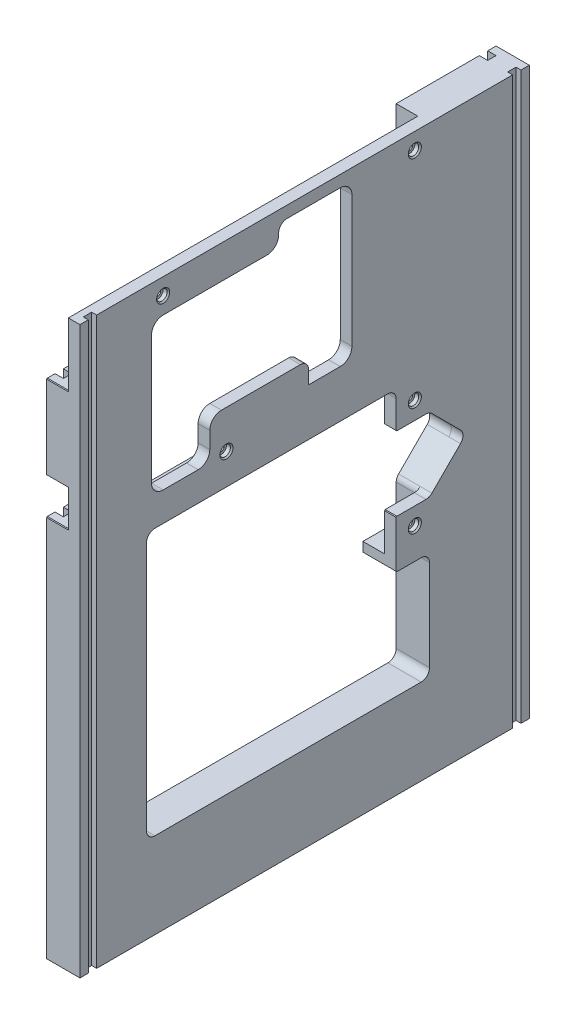
SolidWorks part; units mm, degrees
ref_plane "Front Plane" through (0, 0, 0) normal (0, 0, 1) x (1, 0, 0)
ref_plane "Top Plane" through (0, 0, 0) normal (0, 1, 0) x (1, 0, 0)
ref_plane "Right Plane" through (0, 0, 0) normal (1, 0, 0) x (0, 0, -1)
sketch "Sketch2" plane through (0, 0, 0) normal (1, 0, 0) x (0, 0, -1)
  line L1 (-215.489, 137.2751) -> (127.411, 137.2751)
  line L2 (-215.489, 137.2751) -> (-215.489, -294.5249)
  line L3 (-215.489, -294.5249) -> (127.411, -294.5249)
  line L4 (127.411, 137.2751) -> (127.411, -294.5249)
  dimension "D1" = 342.9
  dimension "D2" = 431.8
extrude "Base" add sketch "Sketch2" along normal blind 25.4
sketch "Sketch3" plane through (0, 0, 0) normal (1, 0, 0) x (0, 0, -1)
  line L0 (-44.039, -294.5249) -> (-44.039, 137.2751) construction
  line L1 (-215.489, -294.5249) -> (127.411, -294.5249) construction
  line L2 (-164.689, -25.9199) -> (-164.689, -229.1199)
  line L3 (-164.689, -229.1199) -> (51.211, -229.1199)
  line L4 (51.211, -146.9509) -> (51.211, -229.1199)
  line L5 (127.411, 137.2751) -> (-215.489, 137.2751) construction
  line L7 (-215.489, 137.2751) -> (-215.489, -294.5249) construction
  line L9 (51.211, -146.9509) -> (25.811, -146.9509)
  line L13 (-164.689, -25.9199) -> (25.811, -25.9199)
  line L14 (25.811, -146.9509) -> (25.811, -25.9199)
  dimension "D1" = 25.4
  dimension "D2" = 163.195
  dimension "D3" = 50.8
  dimension "D4" = 121.031
  dimension "D5" = 190.5
  dimension "D6" = 203.2
extrude "Cut-Extrude3" cut sketch "Sketch3" along normal up to next
sketch "Sketch4" plane through (0, 0, 0) normal (1, 0, 0) x (0, 0, -1)
  line L0 (-215.489, 137.2751) -> (-215.489, -294.5249) construction
  line L1 (19.461, -18.2999) -> (-158.339, -18.2999)
  line L2 (51.211, -15.1249) -> (51.211, 137.2751)
  line L3 (51.211, 137.2751) -> (-202.789, 137.2751)
  line L4 (-164.689, -12.5837) -> (-164.689, -2.4249)
  line L5 (51.211, -146.9509) -> (25.811, -146.9509) construction
  line L6 (25.811, -25.9199) -> (-164.689, -25.9199) construction
  line L7 (-164.689, 24.8801) -> (-215.489, 24.8801)
  line L8 (51.211, -15.1249) -> (51.211, -53.8599)
  line L9 (44.861, -139.3309) -> (25.811, -139.3309)
  line L10 (25.811, -25.9199) -> (25.811, -139.3309)
  line L11 (25.811, -25.9199) -> (-164.689, -25.9199) construction
  line L12 (25.811, -25.9199) -> (19.461, -25.9199)
  line L13 (19.461, -18.2999) -> (19.461, -25.9199)
  line L14 (51.211, -136.1559) -> (51.211, -146.9509)
  line L15 (51.211, -146.9509) -> (44.861, -146.9509)
  line L16 (44.861, -139.3309) -> (44.861, -146.9509)
  line L17 (-44.039, 137.2751) -> (-44.039, -294.5249) construction
  line L18 (-164.689, -12.5837) -> (-164.689, -25.9199)
  line L19 (-164.689, -25.9199) -> (-158.339, -25.9199)
  line L20 (-158.339, -18.2999) -> (-158.339, -25.9199)
  line L22 (-215.489, -294.5249) -> (127.411, -294.5249) construction
  line L23 (51.211, -110.2479) -> (79.405, -82.0539)
  line L24 (-164.689, -2.4249) -> (-215.489, -2.4249)
  line L25 (-215.489, 24.8801) -> (-215.489, -2.4249)
  line L26 (-164.689, 24.8801) -> (-164.689, 89.0151)
  line L27 (-202.789, 137.2751) -> (-215.489, 137.2751)
  line L28 (79.405, -82.0539) -> (51.211, -53.8599)
  line L29 (-164.689, 89.0151) -> (-215.489, 89.0151)
  line L30 (-215.489, 137.2751) -> (-215.489, 90.2851)
  line L31 (-215.489, 90.2851) -> (-215.489, 89.0151)
  line L32 (51.211, -110.2479) -> (51.211, -136.1559)
  dimension "D2" = 7.62
  dimension "D3" = 15.875
  dimension "D4" = 276.606
  dimension "D5" = 25.4
  dimension "D6" = 6.35
  dimension "D7" = 6.35
  dimension "D8" = 7.62
  dimension "D9" = 6.35
  dimension "D10" = 48.26
  dimension "D11" = 43.18
  dimension "D12" = 215.9
  dimension "D13" = 266.7
  dimension "D15" = 45
  dimension "D16" = 29.083
  dimension "D17" = 56.388
extrude "NC pocket" cut sketch "Sketch4" along normal blind 16.51
fillet "Fillet9" radius 6.35 2 edges at (8.255, -110.2479, -51.211) (8.255, -53.8599, -51.211)
fillet "Fillet6" radius 6.35 1 edges at (8.255, -82.0539, -79.405)
hole_wizard "CBORE for M4 SHCS1" positions "Sketch8" profile "Sketch10" counterbore size "M4" standard "ANSI Metric" end condition up to next
sketch "Sketch8" plane through (25.4, 0, 0) normal (1, 0, 0) x (0, 0, -1)
  line L1 (127.411, 137.2751) -> (-215.489, 137.2751) construction
  line L4 (-164.689, -2.4249) -> (-164.689, -229.1199) construction
  line L5 (51.211, -229.1199) -> (51.211, -112.8782) construction
  line L6 (-158.339, -18.2999) -> (19.461, -18.2999) construction
  point P0 (-151.989, 124.5751)
  point P5 (40.035, 124.5751)
  point P7 (40.035, -123.4559)
  point P9 (40.035, -40.5249)
  point P11 (-103.729, -2.4249)
  dimension "D2" = 12.7
  dimension "D3" = 12.7
  dimension "D4" = 11.176
  dimension "D5" = 60.96
  dimension "D6" = 15.875
  dimension "D7" = 11.176
  dimension "D8" = 165.1
  dimension "D9" = 11.176
  dimension "D10" = 82.931
  dimension "D11" = 12.7
sketch "Sketch10" plane through (25.4, 124.5751, 151.989) normal (0, 1, 0) x (0, 0, -1)
  line L0 (0, 0) -> (0, 8.89)
  line L1 (0, 8.89) -> (2.15, 8.89)
  line L3 (2.15, 8.89) -> (2.15, 4)
  line L4 (4, 4) -> (2.15, 4)
  line L5 (4, 4) -> (4, 1)
  line L6 (4, 1) -> (5, 0)
  line L7 (5, 0) -> (0, 0)
  line L8 (-4, 1) -> (-5, 0) construction
  line L11 (0, -6.35) -> (0, 107.95) construction
  dimension "Thru Hole Dia." = 4.3
  dimension "Thru Hole Depth" = 8.89
  dimension "C'Bore Dia." = 8
  dimension "C'Bore Depth" = 4
  dimension "Near C'Sink Dia." = 10
  dimension "Near C'Sink Angle" = 90
sketch "Sketch18" plane through (16.51, 0, 0) normal (-1, 0, 0) x (0, 0, 1)
  circle A0 centre (-40.035, 124.5751) radius 7.1755
  circle A1 centre (151.989, 124.5751) radius 7.1755
  circle A2 centre (103.729, -2.4249) radius 7.1755
  circle A3 centre (-40.035, -40.5249) radius 7.1755
  circle A4 centre (-40.035, -123.4559) radius 7.1755
  dimension "D1" = 14.351
  dimension "D2" = 14.351
  dimension "D3" = 14.351
  dimension "D4" = 14.351
  dimension "D5" = 14.351
extrude "Cut-Extrude4" cut sketch "Sketch18" against normal blind 1.016
hole_wizard "3/8-16 Tapped Hole1" positions "3DSketch1" profile "Sketch14" tap size "3/8-16" standard "ANSI Inch"
sketch3d "3DSketch1"
  line L0 (0, -294.5249, 215.489) -> (0, -294.5249, -127.411) construction
  line L1 (25.4, -294.5249, 215.489) -> (0, -294.5249, 215.489) construction
  point P0 (12.7, -294.5249, -70.261)
  point P2 (12.7, -294.5249, 44.039)
  point P4 (12.7, -294.5249, 158.339)
  dimension "D1" = 12.7
  dimension "D2" = 12.7
  dimension "D3" = 12.7
  dimension "D4" = 114.3
  dimension "D6" = 114.3
  dimension "D5" = 171.45
sketch "Sketch14" plane through (12.7, -294.5249, -70.261) normal (1, 0, 0) x (0, 0, -1)
  line L0 (0, 0) -> (0, 30.3247)
  line L1 (0, 30.3247) -> (3.9687, 27.94)
  line L2 (3.9687, 27.94) -> (3.9687, 0)
  line L5 (3.9687, 0) -> (0, 0)
  line L10 (0, 30.3247) -> (-3.9688, 27.94) construction
  line L11 (0, -6.35) -> (0, 107.95) construction
  dimension "Tap Drill Dia." = 7.9375
  dimension "Tap Drill Depth" = 27.94
  dimension "Drill Angle" = 118
cosmetic thread "Hole Thread1" parameters "D1"=25.4, "D2"=9.525
cosmetic thread "Hole Thread2" parameters "D1"=25.4, "D2"=9.525
cosmetic thread "Hole Thread3" parameters "D1"=25.4, "D2"=9.525
hole_wizard "3/8-16 Tapped Hole2" positions "Sketch15" profile "Sketch17" tap size "3/8-16" standard "ANSI Inch"
sketch "Sketch15" plane through (0, 0, 0) normal (-1, 0, 0) x (0, 0, 1)
  line L0 (215.489, -2.4249) -> (215.489, -294.5249) construction
  line L1 (-127.411, -294.5249) -> (-127.411, 137.2751) construction
  line L2 (215.489, -294.5249) -> (-127.411, -294.5249) construction
  point P0 (190.089, -220.8649)
  point P2 (190.089, -162.4449)
  point P4 (-102.011, -220.8649)
  point P6 (-102.011, -162.4449)
  dimension "D1" = 25.4
  dimension "D2" = 25.4
  dimension "D3" = 25.4
  dimension "D4" = 25.4
  dimension "D5" = 73.66
  dimension "D6" = 58.42
  dimension "D7" = 58.42
  dimension "D8" = 73.66
cosmetic thread "Hole Thread4" parameters "D1"=17.78, "D2"=9.525
cosmetic thread "Hole Thread5" parameters "D1"=17.78, "D2"=9.525
cosmetic thread "Hole Thread6" parameters "D1"=17.78, "D2"=9.525
cosmetic thread "Hole Thread7" parameters "D1"=17.78, "D2"=9.525
sketch "Sketch17" plane through (0, -220.8649, 190.089) normal (0, 1, 0) x (0, 0, 1)
  line L0 (0, 0) -> (0, 22.7047)
  line L1 (0, 22.7047) -> (3.9687, 20.32)
  line L2 (3.9687, 20.32) -> (3.9687, 0)
  line L5 (3.9687, 0) -> (0, 0)
  line L10 (0, 22.7047) -> (-3.9688, 20.32) construction
  line L11 (0, -6.35) -> (0, 107.95) construction
  dimension "Tap Drill Dia." = 7.9375
  dimension "Tap Drill Depth" = 20.32
  dimension "Drill Angle" = 118
sketch "Sketch20" plane through (16.51, 0, 0) normal (-1, 0, 0) x (0, 0, 1)
  line L0 (-51.211, -53.8599) -> (-25.811, -53.8599)
  line L2 (-51.211, -53.8599) -> (-79.405, -82.0539)
  line L3 (-79.405, -82.0539) -> (-51.211, -110.2479)
  line L4 (-25.811, -25.9199) -> (-25.811, -139.3309) construction
  line L6 (-25.811, -53.8599) -> (-25.811, -110.2479)
  line L7 (-25.811, -110.2479) -> (-51.211, -110.2479)
  line L8 (-51.211, -45.3946) -> (-51.211, -54.9122) construction
  line L9 (-51.211, -51.2297) -> (-51.211, 137.2751) construction
  line L10 (-51.211, -116.8371) -> (-51.211, -107.9924) construction
  line L11 (-51.211, -146.9509) -> (-51.211, -112.8782) construction
  line L12 (-74.9149, -77.5638) -> (-53.0709, -55.7198) construction
  line L13 (-53.0709, -108.388) -> (-74.9149, -86.544) construction
extrude "Cut-Extrude5" cut sketch "Sketch20" against normal up to next
fillet "Fillet1" radius 6.35 5 edges at (20.955, -25.9199, 164.689) (12.7, -229.1199, 164.689) (12.7, -229.1199, -51.211) (20.955, -146.9509, -51.211) (20.955, -25.9199, -25.811)
fillet "Fillet2" radius 6.35 3 edges at (20.955, -82.0539, -79.405) (20.955, -110.2479, -51.211) (20.955, -53.8599, -51.211)
chamfer "Chamfer1" distance 0.508 angle 45 9 edges at (8.255, -2.4249, 215.489) (8.255, -2.4249, 164.689) (8.255, 24.8801, 215.489) (8.255, 24.8801, 164.689) (8.255, 89.0151, 215.489) (8.255, 89.0151, 164.689) (12.7, -146.9509, -25.811) (20.955, -110.2479, -25.811) (20.955, -53.8599, -25.811)
sketch "Sketch21" plane through (0, 0, 0) normal (-1, 0, 0) x (0, 0, 1)
  line L0 (215.489, -294.5249) -> (-127.411, -294.5249) construction
  line L1 (209.139, -294.5249) -> (202.789, -294.5249)
  line L2 (209.139, -294.5249) -> (209.139, 137.2751)
  line L3 (209.139, 137.2751) -> (202.789, 137.2751)
  line L4 (202.789, -294.5249) -> (202.789, 137.2751)
  line L5 (-127.411, 137.2751) -> (-51.211, 137.2751) construction
  line L6 (215.489, -2.9329) -> (215.489, -294.5249) construction
  line L7 (-127.411, -294.5249) -> (-127.411, 137.2751) construction
  line L8 (-114.711, -294.5249) -> (-121.061, -294.5249)
  line L9 (-114.711, -294.5249) -> (-114.711, 137.2751)
  line L10 (-114.711, 137.2751) -> (-121.061, 137.2751)
  line L11 (-121.061, -294.5249) -> (-121.061, 137.2751)
  dimension "D1" = 6.35
  dimension "D2" = 6.35
  dimension "D3" = 6.35
  dimension "D4" = 6.35
extrude "Cut-Extrude6" cut sketch "Sketch21" against normal blind 6.35
sketch "Sketch22" plane through (25.4, 0, 0) normal (1, 0, 0) x (0, 0, -1)
  line L0 (-215.489, -294.5249) -> (127.411, -294.5249) construction
  line L1 (-202.789, -294.5249) -> (-209.139, -294.5249)
  line L2 (-202.789, -294.5249) -> (-202.789, 137.2751)
  line L3 (-202.789, 137.2751) -> (-209.139, 137.2751)
  line L4 (-209.139, -294.5249) -> (-209.139, 137.2751)
  line L5 (127.411, 137.2751) -> (-215.489, 137.2751) construction
  line L6 (-215.489, 137.2751) -> (-215.489, -294.5249) construction
  line L7 (127.411, -294.5249) -> (127.411, 137.2751) construction
  line L8 (114.711, 137.2751) -> (121.061, 137.2751)
  line L9 (114.711, 137.2751) -> (114.711, -294.5249)
  line L10 (114.711, -294.5249) -> (121.061, -294.5249)
  line L11 (121.061, 137.2751) -> (121.061, -294.5249)
  dimension "D1" = 6.35
  dimension "D2" = 6.35
  dimension "D3" = 6.35
  dimension "D4" = 6.35
extrude "Cut-Extrude7" cut sketch "Sketch22" against normal blind 3.81
sketch "Sketch23" plane through (25.4, 0, 0) normal (1, 0, 0) x (0, 0, -1)
  line L0 (40.035, -123.4559) -> (40.035, -40.5249) construction
  line L1 (40.035, -113.1031) -> (71.1477, -81.9904)
  line L2 (40.035, -113.1031) -> (8.9223, -81.9904)
  line L3 (71.1477, -81.9904) -> (40.035, -50.8777)
  line L4 (8.9223, -81.9904) -> (40.035, -50.8777)
  line L5 (40.035, -113.1031) -> (40.035, -50.8777) construction
  line L6 (71.1477, -81.9904) -> (8.9223, -81.9904) construction
  circle A0 centre (40.035, -40.5249) radius 5 construction
  circle A1 centre (40.035, -40.5249) radius 5 construction
  circle A2 centre (40.035, -123.4559) radius 5 construction
  circle A3 centre (40.035, -123.4559) radius 5 construction
  point P7 (40.035, -81.9904)
  point P8 (40.035, -81.9904)
  dimension "D1" = 44
  dimension "D2" = 44
sketch "Sketch24" plane through (25.4, 0, 0) normal (1, 0, 0) x (0, 0, -1)
  line L0 (-16.861, 128.3851) -> (-57.501, 128.3851)
  line L1 (-63.851, 122.0351) -> (-63.851, 120.7651)
  line L2 (-72.741, 111.8751) -> (-151.989, 111.8751)
  line L3 (-160.879, 102.9851) -> (-160.879, 5.1951)
  line L4 (-151.989, -3.6949) -> (-125.319, -3.6949)
  line L5 (-116.429, 5.1951) -> (-116.429, 17.8951)
  line L6 (-107.539, 26.7851) -> (-47.341, 26.7851)
  line L7 (-40.991, 20.4351) -> (-40.991, 10.2751)
  line L8 (-40.991, 10.2751) -> (-16.861, 10.2751)
  line L9 (-7.971, 19.1651) -> (-7.971, 119.4951)
  line L10 (114.711, 137.2751) -> (-202.789, 137.2751) construction
  line L11 (51.211, -51.2297) -> (51.211, 137.2751) construction
  line L13 (-164.689, 88.5071) -> (-164.689, 25.3881) construction
  arc A0 (-57.501, 128.3851) -> (-63.851, 122.0351) centre (-57.501, 122.0351) ccw
  arc A1 (-151.989, 111.8751) -> (-160.879, 102.9851) centre (-151.989, 102.9851) ccw
  arc A2 (-151.989, -3.6949) -> (-160.879, 5.1951) centre (-151.989, 5.1951) cw
  arc A3 (-116.429, 5.1951) -> (-125.319, -3.6949) centre (-125.319, 5.1951) cw
  arc A4 (-116.429, 17.8951) -> (-107.539, 26.7851) centre (-107.539, 17.8951) cw
  arc A5 (-7.971, 19.1651) -> (-16.861, 10.2751) centre (-16.861, 19.1651) cw
  arc A6 (-7.971, 119.4951) -> (-16.861, 128.3851) centre (-16.861, 119.4951) ccw
  arc A7 (-63.851, 120.7651) -> (-72.741, 111.8751) centre (-72.741, 120.7651) cw
  arc A8 (-40.991, 20.4351) -> (-47.341, 26.7851) centre (-47.341, 20.4351) ccw
  dimension "D11" = 6.35
  dimension "D12" = 8.89
  dimension "D13" = 6.35
  dimension "D1" = 8.89
  dimension "D2" = 55.88
  dimension "D3" = 59.182
  dimension "D4" = 3.81
  dimension "D5" = 25.4
  dimension "D6" = 118.11
  dimension "D7" = 115.57
  dimension "D8" = 44.45
  dimension "D9" = 16.51
  dimension "D10" = 33.02
extrude "Cut-Extrude8" cut sketch "Sketch24" against normal through all
equation "\"D2@Sketch23\"=\"D1@Sketch23\""
